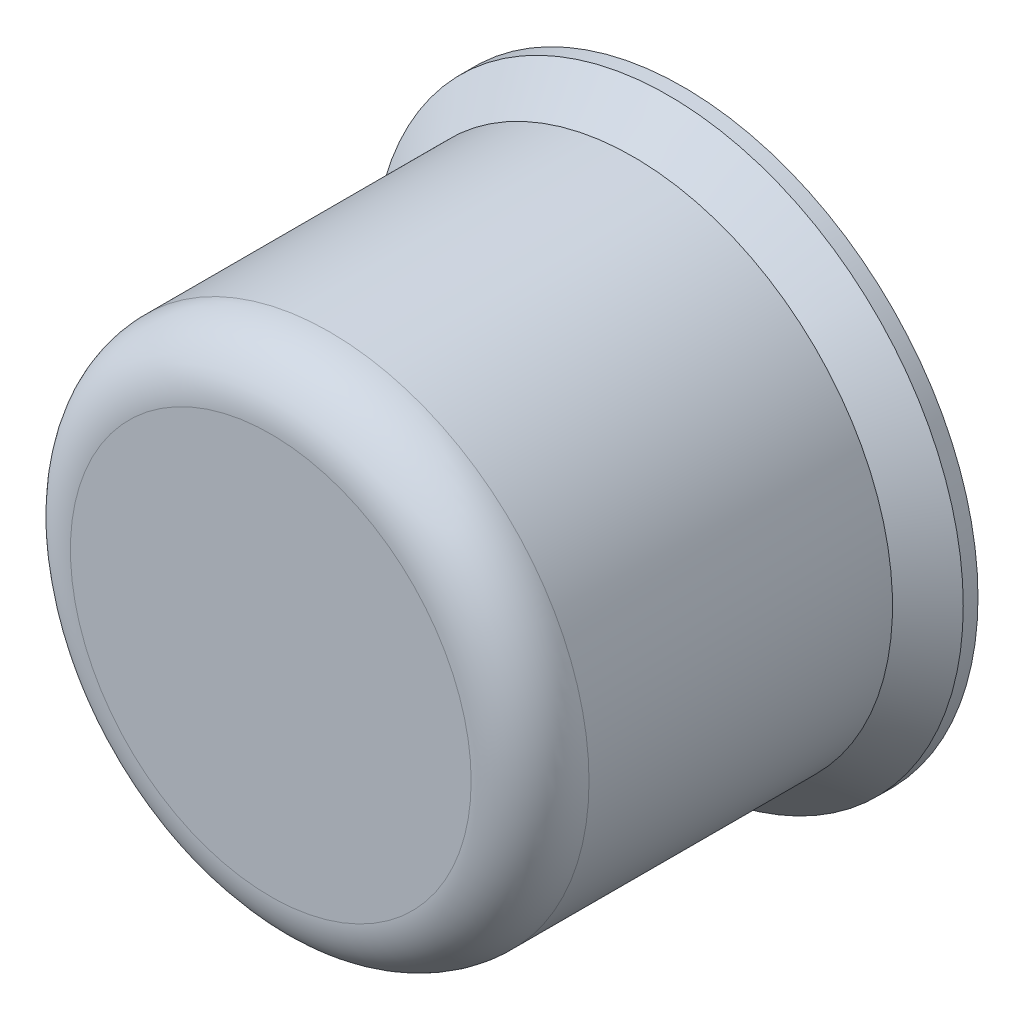
SolidWorks part; units mm, degrees
ref_plane "Front Plane" through (0, 0, 0) normal (0, 0, 1) x (1, 0, 0)
ref_plane "Top Plane" through (0, 0, 0) normal (0, 1, 0) x (1, 0, 0)
ref_plane "Right Plane" through (0, 0, 0) normal (1, 0, 0) x (0, 0, -1)
sketch "Sketch1" plane through (0, 0, 0) normal (0, 0, 1) x (1, 0, 0)
  circle A0 centre (0, 0) radius 5
  dimension "D1" = 10
extrude "Boss-Extrude1" add sketch "Sketch1" along normal blind 1
sketch "Sketch2" plane through (0, 0, 1) normal (0, 0, 1) x (1, 0, 0)
  circle A0 centre (0, 0) radius 4.4
  dimension "D1" = 8.8
extrude "Boss-Extrude2" add sketch "Sketch2" along normal blind 6
fillet "Fillet2" radius 1 1 edges at (4.4, 0, 7)
chamfer "Chamfer1" distance 0.75 angle 45 1 edges at (5, 0, 1)
